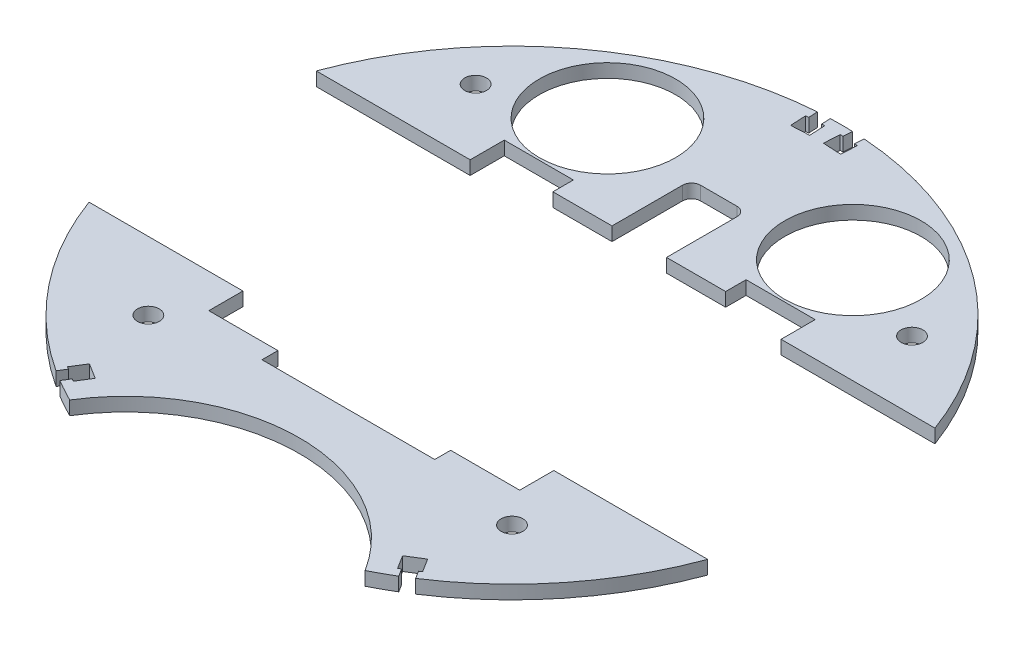
SolidWorks part; units mm, degrees
material "ABS"
ref_plane "Front Plane" through (0, 0, 0) normal (0, 0, 1) x (1, 0, 0)
ref_plane "Top Plane" through (0, 0, 0) normal (0, 1, 0) x (1, 0, 0)
ref_plane "Right Plane" through (0, 0, 0) normal (1, 0, 0) x (0, 0, -1)
sketch "Sketch1" plane through (0, 0, 0) normal (0, 1, 0) x (1, 0, 0)
  line L0 (0, -85) -> (-32.4891, -64.8129) construction
  line L1 (0, -85) -> (0, 0) construction
  arc A0 (32.4891, -64.8129) -> (-32.4891, -64.8129) centre (0, 0) ccw
  arc A1 (32.4891, -64.8129) -> (-32.4891, -64.8129) centre (0, -85) ccw
  dimension "D1" = 145
  dimension "D2" = 76.5
  dimension "D3" = 85
extrude "Boss-Extrude1" add sketch "Sketch1" along normal blind 3
sketch "solenoid placement" plane through (0, 3, 0) normal (0, 1, 0) x (1, 0, 0)
  line L4 (-19, -36) -> (19, -36)
  line L5 (-19, 28) -> (-19, -36)
  line L10 (19, 28) -> (-19, 28)
  line L11 (19, -36) -> (19, 28)
  line L12 (-19, -36) -> (19, -36)
  line L13 (-19, 28) -> (-19, -36)
  line L14 (19, 28) -> (-19, 28)
  line L15 (19, -36) -> (19, 28)
  dimension "D1" = 0
extrude "Cut-Extrude1" cut sketch "solenoid placement" against normal through all
sketch "Sketch7" plane through (0, 3, 0) normal (0, 1, 0) x (1, 0, 0)
  circle A3 centre (27, 48) radius 15
  circle A4 centre (27, 48) radius 15
  circle A5 centre (-27, 48) radius 15
  circle A6 centre (-27, 48) radius 15
  dimension "D1" = 0
  dimension "D2" = 0
extrude "Cut-Extrude6" cut sketch "Sketch7" against normal through all
sketch "Sketch8" plane through (0, 3, 0) normal (0, 1, 0) x (1, 0, 0)
  circle A1 centre (40, -40) radius 2.4
  circle A2 centre (40, -40) radius 2.4
  circle A3 centre (-40, -40) radius 2.4
  circle A4 centre (-40, -40) radius 2.4
  circle A5 centre (48, 40) radius 2.4
  circle A6 centre (48, 40) radius 2.4
  circle A7 centre (-48, 40) radius 2.4
  circle A8 centre (-48, 40) radius 2.4
  dimension "D1" = 0
  dimension "D2" = 0
  dimension "D3" = 0
  dimension "D4" = 0
extrude "Cut-Extrude7" cut sketch "Sketch8" against normal through all
sketch "Sketch3" plane through (0, 3, 0) normal (0, 1, 0) x (1, 0, 0)
  line L1 (-34.2, -32.5) -> (-22.2, -32.5)
  line L2 (-34.2, 25) -> (-68.0533, 25)
  line L3 (-34.2, 32.5) -> (-22.2, 32.5)
  line L4 (-22.2, -32.5) -> (-22.2, 32.5) construction
  line L8 (0, 0) -> (0, 72.5) construction
  line L17 (-34.2, -32.5) -> (-34.2, -25)
  line L18 (-34.2, -25) -> (-68.0533, -25)
  line L19 (-34.2, 25) -> (-34.2, 32.5)
  line L21 (-22.2, 32.5) -> (-19, 32.5)
  line L22 (-22.2, 32.5) -> (-22.2, -32.5) construction
  line L23 (-22.2, -32.5) -> (-19, -32.5)
  line L24 (-19, 32.5) -> (-19, -32.5)
  line L25 (22.2, 32.5) -> (22.2, -32.5) construction
  line L26 (22.2, -32.5) -> (22.2, 32.5) construction
  line L27 (19, 32.5) -> (19, -32.5)
  line L28 (22.2, -32.5) -> (19, -32.5)
  line L29 (22.2, 32.5) -> (19, 32.5)
  line L30 (34.2, 25) -> (34.2, 32.5)
  line L31 (34.2, -25) -> (68.0533, -25)
  line L32 (34.2, -32.5) -> (34.2, -25)
  line L33 (34.2, 32.5) -> (22.2, 32.5)
  line L34 (34.2, 25) -> (68.0533, 25)
  line L35 (34.2, -32.5) -> (22.2, -32.5)
  line L36 (-19, 28) -> (-19, -36) construction
  arc A0 (32.4891, -64.8129) -> (-32.4891, -64.8129) centre (0, 0) ccw construction
  arc A2 (68.0533, 25) -> (68.0533, -25) centre (0, 0) cw
  arc A3 (-68.0533, 25) -> (-68.0533, -25) centre (0, 0) ccw
  point P31 (-34.2, -32.5)
  dimension "D1" = 50
extrude "Cut-Extrude3" cut sketch "Sketch3" against normal through all
sketch "Sketch9" plane through (0, 3, 0) normal (0, 1, 0) x (1, 0, 0)
  line L0 (6, 43.5) -> (6, 28)
  line L1 (-6, 43.5) -> (-6, 28)
  line L2 (19, 28) -> (-19, 28) construction
  line L8 (-6, 28) -> (6, 28)
  line L10 (4, 45.5) -> (-4, 45.5)
  arc A0 (-6, 43.5) -> (-4, 45.5) centre (-4, 43.5) cw
  arc A1 (6, 43.5) -> (4, 45.5) centre (4, 43.5) ccw
  point P5 (0, 28)
  point P6 (0, 28)
  point P16 (-6, 45.5)
  point P19 (6, 45.5)
  dimension "D3" = 2
  dimension "D2" = 12
  dimension "D1" = 17.5
extrude "Cut-Extrude8" cut sketch "Sketch9" against normal through all
sketch "Sketch10" plane through (0, 3, 0) normal (0, 1, 0) x (1, 0, 0)
  line L0 (0, 0) -> (0, 72.5) construction
  line L1 (0, 0) -> (3.7944, 72.4006) construction
  line L2 (1.5092, 67.0129) -> (5.5038, 66.8035)
  line L3 (1.5092, 67.0129) -> (1.6924, 70.5081)
  line L4 (5.5038, 66.8035) -> (5.6869, 70.2987)
  line L5 (1.6924, 70.5081) -> (2.3415, 70.474)
  line L6 (2.3415, 70.474) -> (2.4462, 72.4713)
  line L7 (2.4462, 72.4713) -> (5.1425, 72.33)
  line L8 (5.1425, 72.33) -> (5.0378, 70.3327)
  line L9 (5.0378, 70.3327) -> (5.6869, 70.2987)
  line L10 (-5.0378, 70.3327) -> (-5.6869, 70.2987)
  line L11 (-5.1425, 72.33) -> (-5.0378, 70.3327)
  line L12 (-2.4462, 72.4713) -> (-5.1425, 72.33)
  line L13 (-2.3415, 70.474) -> (-2.4462, 72.4713)
  line L14 (-1.6924, 70.5081) -> (-2.3415, 70.474)
  line L15 (-5.5038, 66.8035) -> (-5.6869, 70.2987)
  line L16 (-1.5092, 67.0129) -> (-1.6924, 70.5081)
  line L17 (-1.5092, 67.0129) -> (-5.5038, 66.8035)
  line L18 (37.2007, -55.7594) -> (33.8085, -57.8791)
  line L19 (37.2007, -55.7594) -> (39.0554, -58.7276)
  line L20 (33.8085, -57.8791) -> (35.6632, -60.8472)
  line L21 (39.0554, -58.7276) -> (38.5042, -59.072)
  line L22 (38.5042, -59.072) -> (39.564, -60.7681)
  line L23 (39.564, -60.7681) -> (37.2743, -62.1989)
  line L24 (37.2743, -62.1989) -> (36.2144, -60.5028)
  line L25 (36.2144, -60.5028) -> (35.6632, -60.8472)
  line L26 (0, 0) -> (38.4191, -61.4835) construction
  line L27 (0, 0) -> (0, -85) construction
  line L28 (-33.8085, -57.8791) -> (-37.2007, -55.7594)
  line L29 (-33.8085, -57.8791) -> (-35.6632, -60.8472)
  line L30 (-37.2007, -55.7594) -> (-39.0554, -58.7276)
  line L31 (-35.6632, -60.8472) -> (-36.2144, -60.5028)
  line L32 (-36.2144, -60.5028) -> (-37.2743, -62.1989)
  line L33 (-37.2743, -62.1989) -> (-39.564, -60.7681)
  line L34 (-39.564, -60.7681) -> (-38.5042, -59.072)
  line L35 (-38.5042, -59.072) -> (-39.0554, -58.7276)
  line L36 (0, 0) -> (-38.4191, -61.4835) construction
  arc A1 (68.0533, 25) -> (-68.0533, 25) centre (0, 0) ccw construction
  point P1 (3.5065, 66.9082)
  point P15 (3.7944, 72.4006)
  point P36 (0, 0)
  point P49 (0, 0)
  dimension "D1" = 3.5
  dimension "D2" = 4
  dimension "D3" = 3
  dimension "D4" = 2.7
  dimension "D5" = 2
  dimension "D7" = 32
  dimension "D9" = 32
  dimension "D6" = 2
  dimension "D8" = 2
extrude "Cut-Extrude9" cut sketch "Sketch10" against normal through all
equation "\"smallPulleyTeeth\"= 30"
equation "\"largePulleyTeeth\"= 30"
equation "\"eighthThick\"= 3.0mm"
equation "\"sixteenthThick\" = 1.7mm"
equation "\"quarterThick\"=6.0mm"
equation "\"OD\" = 145mm"
equation "\"puckAngle\" = 60.5deg"
equation "\"D1@Sketch1\"=\"OD\""
equation "\"puckDiam\" = 76.5mm"
equation "\"D2@Sketch1\"=\"puckDiam\""
equation "\"D1@Boss-Extrude1\"=\"eighthThick\""
equation "\"axlePress\" = 5.9mm"
equation "\"press\" = 0.2mm"
equation "\"wheelClear\" = 0.3mm"
equation "\"10-32clear\" = 4.8mm"
equation "\"6-32clear\" = 3.3mm"
equation "\"8-32clear\" = 4.0mm"
equation "\"4-40clear\" = 3.0mm"
equation "\"wheelHeight\" = 22mm"
equation "\"wheelWell\" = 65mm"
equation "\"puckDist\" = 85mm"
equation "\"D3@Sketch1\"=\"puckDist\""
equation "\"scoopFillet\" = 5mm"
equation "\"10-32tap\" = 4.45mm"
equation "\"ledSmall\" = 3.1mm"
equation "\"ledLarge\" = 4.2mm"
equation "\"ledLength\" = 4.2mm"
equation "\"4-40close\" = 2.7mm"
equation "\"4-40nutThick\" = 2.2mm"
equation "\"4-40nutWidth\" = 6.2mm"
equation "\"4-40insertHeight\" = 3.5mm"
equation "\"4-40insert\" = 4mm"
equation "\"D1@Sketch10\"=\"4-40insertHeight\""
equation "\"D2@Sketch10\"=\"4-40insert\""
equation "\"D4@Sketch10\"=\"4-40close\""
